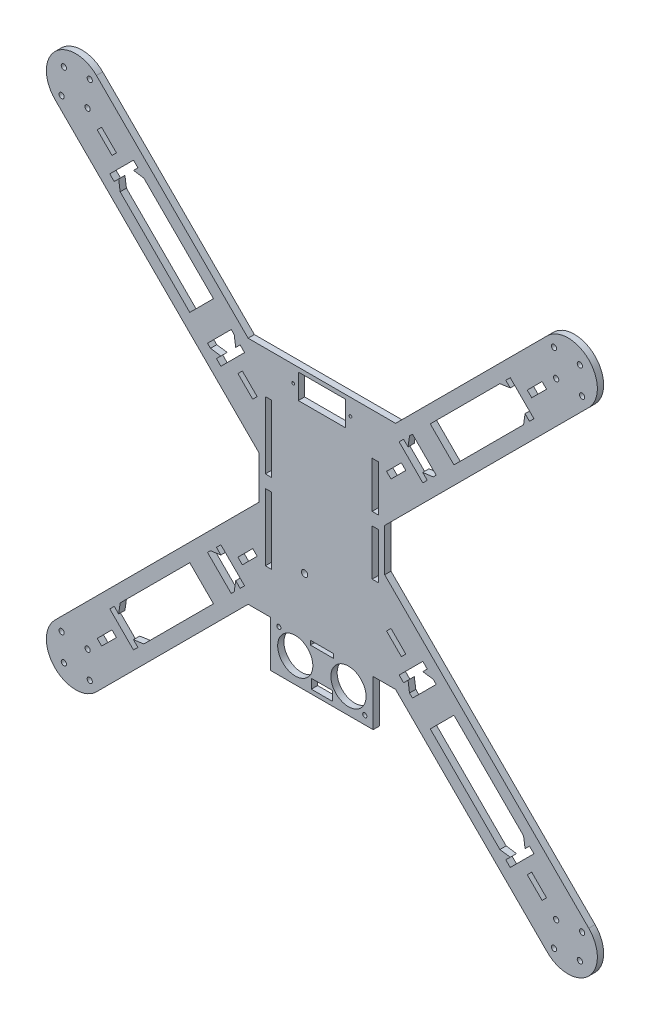
SolidWorks part; units mm, degrees
material "Custom Plastic"
ref_plane "Front Plane" through (0, 0, 0) normal (0, 0, 1) x (1, 0, 0)
ref_plane "Top Plane" through (0, 0, 0) normal (0, 1, 0) x (1, 0, 0)
ref_plane "Right Plane" through (0, 0, 0) normal (1, 0, 0) x (0, 0, -1)
sketch "Sketch1" plane through (0, 0, 0) normal (0, 0, 1) x (1, 0, 0)
  line L0 (117.5, 117.5) -> (-117.5, 117.5) construction
  line L1 (-117.5, 117.5) -> (117.5, -117.5) construction
  line L2 (117.5, -117.5) -> (-117.5, -117.5) construction
  line L3 (-117.5, -117.5) -> (117.5, 117.5) construction
  line L4 (117.5, 117.5) -> (117.5, -117.5) construction
  line L5 (-117.5, 117.5) -> (-117.5, -117.5) construction
  line L6 (0, 117.5) -> (0, -117.5) construction
  line L7 (35.201, 55) -> (-35.201, 55)
  line L8 (-30, 55) -> (30, 55) construction
  line L9 (-35.201, 55) -> (-107.6005, 127.3995)
  line L10 (-127.3995, 107.6005) -> (-30, 10.201)
  line L11 (-117.5, 0) -> (117.5, 0) construction
  line L12 (-30, 10.201) -> (-30, -10.201)
  line L13 (30, 55) -> (30, -55) construction
  line L14 (30, -55) -> (-30, -55) construction
  line L15 (-30, -55) -> (-30, 55) construction
  line L16 (30, 55) -> (-30, -55) construction
  line L17 (-24.5, -55) -> (-24.5, -77)
  line L18 (-127.3995, -107.6005) -> (-30, -10.201)
  line L19 (-24.5, -77) -> (24.5, -77)
  line L20 (-35.201, -55) -> (-107.6005, -127.3995)
  line L21 (35.201, -55) -> (24.5, -55)
  line L22 (35.201, -55) -> (107.6005, -127.3995)
  line L23 (127.3995, -107.6005) -> (30, -10.201)
  line L24 (30, 10.201) -> (30, -10.201)
  line L25 (127.3995, 107.6005) -> (30, 10.201)
  line L26 (35.201, 55) -> (107.6005, 127.3995)
  line L27 (24.5, -55) -> (24.5, -77)
  line L28 (-24.5, -55) -> (-35.201, -55)
  arc A0 (-107.6005, 127.3995) -> (-127.3995, 107.6005) centre (-117.5, 117.5) ccw
  arc A12 (-107.6005, -127.3995) -> (-127.3995, -107.6005) centre (-117.5, -117.5) cw
  arc A16 (107.6005, -127.3995) -> (127.3995, -107.6005) centre (117.5, -117.5) ccw
  arc A24 (107.6005, 127.3995) -> (127.3995, 107.6005) centre (117.5, 117.5) cw
  point P3 (0, 0)
  point P18 (0, 0)
  point P21 (0, -77)
  point P33 (-117.5, 117.5)
  point P34 (-30, 0)
  point P65 (0, -55)
  point P80 (0, 55)
  dimension "D3" = 14
  dimension "D8" = 24.5
  dimension "D7" = 22
  dimension "D1" = 235
  dimension "D2" = 235
  dimension "D4" = 60
  dimension "D5" = 110
  dimension "D6" = 28
extrude "Boss-Extrude1" add sketch "Sketch1" against normal blind 3
sketch "Sketch4" plane through (0, 0, 0) normal (0, 0, 1) x (1, 0, 0)
  line L0 (0, 0) -> (0, 55) construction
  line L1 (35.201, 55) -> (-35.201, 55) construction
  line L2 (0, 0) -> (-30, 0) construction
  line L3 (-30, 10.201) -> (-30, -10.201) construction
  line L4 (-30, 0) -> (-30, 10.201) construction
  line L5 (-30, 10.201) -> (-127.3995, 107.6005) construction
  line L6 (-35.201, 55) -> (-107.6005, 127.3995) construction
  line L7 (-107.6005, 127.3995) -> (-127.3995, 107.6005) construction
  line L8 (-110.7825, 124.2175) -> (-124.2175, 110.7825) construction
  line L9 (-123.1569, 123.1569) -> (-111.8431, 111.8431) construction
  circle A20 centre (-110.7825, 124.2175) radius 1.25
  circle A21 centre (-124.2175, 110.7825) radius 1.25
  circle A22 centre (-123.1569, 123.1569) radius 1.25
  circle A23 centre (-111.8431, 111.8431) radius 1.25
  circle A24 centre (111.8431, 111.8431) radius 1.25
  circle A25 centre (110.7825, 124.2175) radius 1.25
  circle A26 centre (123.1569, 123.1569) radius 1.25
  circle A27 centre (124.2175, 110.7825) radius 1.25
  circle A28 centre (111.8431, -111.8431) radius 1.25
  circle A29 centre (124.2175, -110.7825) radius 1.25
  circle A30 centre (123.1569, -123.1569) radius 1.25
  circle A31 centre (110.7825, -124.2175) radius 1.25
  circle A32 centre (-111.8431, -111.8431) radius 1.25
  circle A33 centre (-110.7825, -124.2175) radius 1.25
  circle A34 centre (-123.1569, -123.1569) radius 1.25
  circle A35 centre (-124.2175, -110.7825) radius 1.25
  point P16 (-117.5, 117.5)
  point P19 (-117.5, 117.5)
  point P26 (-117.5, 117.5)
  point P62 (0, 0)
  dimension "D4" = 2.5
  dimension "D2" = 19
  dimension "D3" = 16
extrude "Cut-Extrude1" cut sketch "Sketch4" against normal blind 3
sketch "Sketch5" plane through (0, 0, 0) normal (0, 0, 1) x (1, 0, 0)
  line L7 (-11.25, 53) -> (-11.25, 41.2)
  line L8 (-11.25, 41.2) -> (11.25, 41.2)
  line L9 (11.25, 41.2) -> (11.25, 53)
  line L10 (11.25, 53) -> (-11.25, 53)
  line L12 (0, 53) -> (0, 41.2) construction
  line L13 (-13.65, 47.1) -> (13.65, 47.1) construction
  line L14 (35.201, 55) -> (-35.201, 55) construction
  circle A2 centre (-13.65, 47.1) radius 0.65
  circle A3 centre (13.65, 47.1) radius 0.65
  point P20 (0, 47.1)
  point P21 (0, 47.1)
  point P26 (0, 55)
  dimension "D8" = 1.3
  dimension "D9" = 1.3
  dimension "D10" = 27.3
  dimension "D11" = 22.5
  dimension "D12" = 11.8
  dimension "D13" = 2
extrude "Cut-Extrude2" cut sketch "Sketch5" against normal blind 3
sketch "Sketch6" plane through (0, 0, 0) normal (0, 0, 1) x (1, 0, 0)
  line L1 (-11.25, 41.2) -> (11.25, 41.2) construction
  circle A0 centre (-8.25, -28.8) radius 1.5
  dimension "D3" = 3
  dimension "D1" = 70
  dimension "D2" = 3
extrude "Cut-Extrude3" cut sketch "Sketch6" against normal blind 3
sketch "Sketch7" plane through (0, 0, 0) normal (0, 0, 1) x (1, 0, 0)
  line L0 (-22.5, -55) -> (-22.5, -75) construction
  line L5 (-22.5, -75) -> (22.5, -75) construction
  line L6 (22.5, -75) -> (22.5, -55) construction
  line L7 (22.5, -55) -> (-22.5, -55) construction
  line L8 (0, -55) -> (0, -75) construction
  line L9 (-12.7, -65) -> (0, -65) construction
  line L10 (-24.5, -77) -> (24.5, -77) construction
  line L11 (-24.5, -55) -> (-24.5, -77) construction
  line L12 (-5.5, -55) -> (-5.5, -57)
  line L13 (-5.5, -57) -> (5.5, -57)
  line L15 (5.5, -55) -> (-5.5, -55)
  line L16 (-5, -75) -> (-5, -70.5)
  line L17 (-5, -70.5) -> (5, -70.5)
  line L21 (5, -75) -> (-5, -75)
  line L22 (5.5, -55) -> (5.5, -57)
  line L23 (5, -75) -> (5, -70.5)
  circle A5 centre (-20.5, -57) radius 1
  circle A6 centre (-12.7, -65) radius 8.4
  circle A7 centre (12.7, -65) radius 8.4
  circle A8 centre (20.5, -73) radius 1
  point P25 (0, -57)
  point P26 (0, -70.5)
  dimension "D3" = 2
  dimension "D6" = 20
  dimension "D13" = 5
  dimension "D5" = 45
  dimension "D1" = 2
  dimension "D4" = 16.8
  dimension "D14" = 2
  dimension "D2" = 2
  dimension "D7" = 2
  dimension "D8" = 2
  dimension "D9" = 12.7
  dimension "D10" = 5.5
  dimension "D11" = 2
  dimension "D12" = 4.5
  dimension "D15" = 2
  dimension "D16" = 2
extrude "Cut-Extrude4" cut sketch "Sketch7" against normal blind 3
sketch "Sketch8" plane through (0, 0, 0) normal (0, 0, 1) x (1, 0, 0)
  line L0 (101.2365, -89.9228) -> (89.9228, -101.2365)
  line L1 (89.9228, -101.2365) -> (87.8015, -99.1152)
  line L2 (36.8898, -48.2035) -> (48.2035, -36.8898)
  line L3 (48.2035, -36.8898) -> (50.3249, -39.0111)
  line L4 (105.4792, -85.6802) -> (85.6802, -105.4792) construction
  line L5 (127.3995, -107.6005) -> (30, -10.201) construction
  line L6 (35.201, -55) -> (107.6005, -127.3995) construction
  line L7 (40.0718, -37.9505) -> (37.9505, -40.0718)
  line L8 (115.8431, -107.8431) -> (111.8431, -111.8431) construction
  line L9 (37.9505, -40.0718) -> (30.8794, -33.0007)
  line L10 (50.3249, 39.0111) -> (48.2035, 36.8898)
  line L11 (30.8794, -33.0007) -> (33.0007, -30.8794)
  line L12 (33.0007, -30.8794) -> (40.0718, -37.9505)
  line L13 (42.5467, -42.5467) -> (39.0111, -39.0111) construction
  line L14 (35.201, -55) -> (107.6005, -127.3995) construction
  line L15 (100.1759, -98.0546) -> (98.0546, -100.1759)
  line L16 (98.0546, -100.1759) -> (105.1256, -107.247)
  line L17 (105.1256, -107.247) -> (107.247, -105.1256)
  line L18 (107.247, -105.1256) -> (100.1759, -98.0546)
  line L19 (99.1152, -99.1152) -> (95.5797, -95.5797) construction
  line L20 (-101.2365, -89.9228) -> (-99.1152, -87.8015)
  line L21 (-100.1759, -98.0546) -> (-107.247, -105.1256)
  line L22 (-107.247, -105.1256) -> (-105.1256, -107.247)
  line L23 (-105.1256, -107.247) -> (-98.0546, -100.1759)
  line L24 (-98.0546, -100.1759) -> (-100.1759, -98.0546)
  line L25 (-89.9228, -101.2365) -> (-101.2365, -89.9228)
  line L26 (-36.8898, -48.2035) -> (-39.0111, -50.3249)
  line L27 (-48.2035, -36.8898) -> (-36.8898, -48.2035)
  line L28 (-37.9505, -40.0718) -> (-40.0718, -37.9505)
  line L29 (-30.8794, -33.0007) -> (-37.9505, -40.0718)
  line L30 (-40.0718, -37.9505) -> (-33.0007, -30.8794)
  line L31 (-33.0007, -30.8794) -> (-30.8794, -33.0007)
  line L32 (-89.9228, 101.2365) -> (-87.8015, 99.1152)
  line L33 (-98.0546, 100.1759) -> (-105.1256, 107.247)
  line L34 (-105.1256, 107.247) -> (-107.247, 105.1256)
  line L35 (-107.247, 105.1256) -> (-100.1759, 98.0546)
  line L36 (-100.1759, 98.0546) -> (-98.0546, 100.1759)
  line L37 (-101.2365, 89.9228) -> (-89.9228, 101.2365)
  line L38 (-48.2035, 36.8898) -> (-50.3249, 39.0111)
  line L39 (-36.8898, 48.2035) -> (-48.2035, 36.8898)
  line L40 (-40.0718, 37.9505) -> (-37.9505, 40.0718)
  line L41 (-33.0007, 30.8794) -> (-40.0718, 37.9505)
  line L42 (-37.9505, 40.0718) -> (-30.8794, 33.0007)
  line L43 (-30.8794, 33.0007) -> (-33.0007, 30.8794)
  line L44 (101.2365, 89.9228) -> (99.1152, 87.8015)
  line L45 (100.1759, 98.0546) -> (107.247, 105.1256)
  line L46 (107.247, 105.1256) -> (105.1256, 107.247)
  line L47 (105.1256, 107.247) -> (98.0546, 100.1759)
  line L48 (98.0546, 100.1759) -> (100.1759, 98.0546)
  line L49 (89.9228, 101.2365) -> (101.2365, 89.9228)
  line L50 (36.8898, 48.2035) -> (39.0111, 50.3249)
  line L51 (48.2035, 36.8898) -> (36.8898, 48.2035)
  line L52 (37.9505, 40.0718) -> (40.0718, 37.9505)
  line L53 (30.8794, 33.0007) -> (37.9505, 40.0718)
  line L54 (40.0718, 37.9505) -> (33.0007, 30.8794)
  line L55 (33.0007, 30.8794) -> (30.8794, 33.0007)
  line L56 (30, 10.201) -> (127.3995, 107.6005) construction
  line L57 (41.8396, 53.1533) -> (84.9731, 96.2868)
  line L58 (96.2868, 84.9731) -> (53.1533, 41.8396)
  line L59 (87.8015, 99.1152) -> (89.9228, 101.2365)
  line L60 (99.1152, -87.8015) -> (96.9939, -89.9228)
  line L61 (-96.2868, -84.9731) -> (-53.1533, -41.8396)
  line L62 (96.9939, -89.9228) -> (96.2868, -84.9731)
  line L63 (99.1152, -87.8015) -> (101.2365, -89.9228)
  line L64 (87.8015, -99.1152) -> (89.9228, -96.9939)
  line L65 (-87.8015, -99.1152) -> (-89.9228, -101.2365)
  line L66 (89.9228, -96.9939) -> (84.9731, -96.2868)
  line L67 (84.9731, -96.2868) -> (41.8396, -53.1533)
  line L68 (50.3249, -39.0111) -> (48.2035, -41.1325)
  line L69 (48.2035, -41.1325) -> (53.1533, -41.8396)
  line L70 (53.1533, -41.8396) -> (96.2868, -84.9731)
  line L71 (39.0111, -50.3249) -> (41.1325, -48.2035)
  line L72 (41.1325, -48.2035) -> (41.8396, -53.1533)
  line L73 (39.0111, -50.3249) -> (36.8898, -48.2035)
  line L74 (-89.9228, -96.9939) -> (-84.9731, -96.2868)
  line L75 (-87.8015, -99.1152) -> (-89.9228, -96.9939)
  line L76 (-96.9939, -89.9228) -> (-96.2868, -84.9731)
  line L77 (-99.1152, -87.8015) -> (-96.9939, -89.9228)
  line L78 (-41.1325, -48.2035) -> (-41.8396, -53.1533)
  line L79 (-39.0111, -50.3249) -> (-41.1325, -48.2035)
  line L80 (-48.2035, -41.1325) -> (-53.1533, -41.8396)
  line L81 (-50.3249, -39.0111) -> (-48.2035, -41.1325)
  line L82 (-96.9939, 89.9228) -> (-96.2868, 84.9731)
  line L83 (-99.1152, 87.8015) -> (-96.9939, 89.9228)
  line L84 (-89.9228, 96.9939) -> (-84.9731, 96.2868)
  line L85 (-87.8015, 99.1152) -> (-89.9228, 96.9939)
  line L86 (-48.2035, 41.1325) -> (-53.1533, 41.8396)
  line L87 (-50.3249, 39.0111) -> (-48.2035, 41.1325)
  line L88 (-41.1325, 48.2035) -> (-41.8396, 53.1533)
  line L89 (-39.0111, 50.3249) -> (-41.1325, 48.2035)
  line L90 (89.9228, 96.9939) -> (84.9731, 96.2868)
  line L91 (87.8015, 99.1152) -> (89.9228, 96.9939)
  line L92 (96.9939, 89.9228) -> (96.2868, 84.9731)
  line L93 (99.1152, 87.8015) -> (96.9939, 89.9228)
  line L94 (41.1325, 48.2035) -> (41.8396, 53.1533)
  line L95 (39.0111, 50.3249) -> (41.1325, 48.2035)
  line L96 (48.1429, 41.1931) -> (53.1533, 41.8396)
  line L97 (50.3249, 39.0111) -> (48.1429, 41.1931)
  line L98 (-39.0111, 50.3249) -> (-36.8898, 48.2035)
  line L99 (-53.1533, 41.8396) -> (-96.2868, 84.9731)
  line L100 (-99.1152, 87.8015) -> (-101.2365, 89.9228)
  line L101 (-84.9731, 96.2868) -> (-41.8396, 53.1533)
  line L102 (-41.8396, -53.1533) -> (-84.9731, -96.2868)
  line L103 (-50.3249, -39.0111) -> (-48.2035, -36.8898)
  line L104 (96.2868, 84.9731) -> (84.9731, 96.2868) construction
  line L105 (53.1533, 41.8396) -> (41.8396, 53.1533) construction
  point P10 (95.5797, -95.5797)
  point P11 (95.5797, -95.5797)
  point P18 (-49.2642, 40.0718)
  point P19 (-49.2642, -40.0718)
  point P68 (0, 0)
  point P122 (0, 0)
  dimension "D1" = 23
  dimension "D2" = 75
  dimension "D3" = 3
  dimension "D4" = 10
  dimension "D5" = 5
  dimension "D6" = 6
  dimension "D7" = 3
  dimension "D8" = 10
  dimension "D9" = 5
  dimension "D11" = 6
  dimension "D12" = 3
  dimension "D13" = 4
  dimension "D14" = 3
  dimension "D15" = 3
  dimension "D16" = 4
  dimension "D17" = 3
  dimension "D18" = 3
  dimension "D19" = 4
  dimension "D20" = 3
  dimension "D21" = 3
  dimension "D22" = 4
  dimension "D23" = 3
  dimension "D24" = 3
  dimension "D25" = 4
  dimension "D26" = 3
  dimension "D27" = 4
  dimension "D28" = 3
  dimension "D29" = 3
  dimension "D30" = 4
  dimension "D31" = 4
  dimension "D32" = 3
  dimension "D33" = 3
  dimension "D34" = 4
  dimension "D35" = 4
  dimension "D36" = 3
  dimension "D37" = 3
  dimension "D38" = 4
  dimension "D39" = 4
  dimension "D40" = 3
  dimension "D41" = 3
  dimension "D42" = 4
  dimension "D43" = 4
  dimension "D10" = 4
extrude "Cut-Extrude5" cut sketch "Sketch8" against normal through all
sketch "Sketch9" plane through (-5.6569, 5.6569, 0) normal (0.7071, -0.7071, 0) x (0, 0, -1)
  line L0 (3, 128.1701) -> (3, 67.1701) construction
  line L1 (3, 81.1701) -> (0, 81.1701)
  line L2 (3, 81.1701) -> (3, 69.1701)
  line L3 (3, 69.1701) -> (0, 69.1701)
  line L4 (0, 81.1701) -> (0, 69.1701)
  line L5 (0, 128.1701) -> (0, 67.1701) construction
  line L6 (0, 0) -> (28.0274, 0) construction
  line L7 (3, 63.1701) -> (0, 63.1701) construction
  dimension "D1" = 6
  dimension "D2" = 12
extrude "Boss-Extrude2" add sketch "Sketch9" along normal up to next
sketch "Sketch11" plane through (5.6569, 5.6569, 0) normal (-0.7071, -0.7071, 0) x (0, 0, 1)
  line L0 (-3, -128.1701) -> (-3, -67.1701) construction
  line L1 (-3, -69.1701) -> (0, -69.1701)
  line L2 (-3, -69.1701) -> (-3, -81.1701)
  line L3 (-3, -81.1701) -> (0, -81.1701)
  line L4 (0, -69.1701) -> (0, -81.1701)
  line L5 (0, -128.1701) -> (0, -67.1701) construction
  line L6 (-3, -63.1701) -> (0, -63.1701) construction
  dimension "D1" = 6
  dimension "D2" = 12
extrude "Boss-Extrude3" add sketch "Sketch11" along normal up to next
sketch "Sketch12" plane through (5.6569, -5.6569, 0) normal (-0.7071, 0.7071, 0) x (0, 0, 1)
  line L0 (-3, -128.1701) -> (-3, -67.1701) construction
  line L1 (-3, -69.1701) -> (0, -69.1701)
  line L2 (-3, -69.1701) -> (-3, -81.1701)
  line L3 (-3, -81.1701) -> (0, -81.1701)
  line L4 (0, -69.1701) -> (0, -81.1701)
  line L5 (0, -128.1701) -> (0, -67.1701) construction
  dimension "D1" = 6
  dimension "D2" = 12
extrude "Boss-Extrude4" add sketch "Sketch12" along normal up to next
sketch "Sketch13" plane through (5.6569, 5.6569, 0) normal (-0.7071, -0.7071, 0) x (0, 0, 1)
  line L0 (-3, 67.1701) -> (-3, 128.1701) construction
  line L1 (-3, 69.1701) -> (0, 69.1701)
  line L2 (-3, 69.1701) -> (-3, 81.1701)
  line L3 (-3, 81.1701) -> (0, 81.1701)
  line L4 (0, 69.1701) -> (0, 81.1701)
  line L5 (0, 67.1701) -> (0, 128.1701) construction
  dimension "D1" = 6
  dimension "D2" = 12
extrude "Boss-Extrude5" add sketch "Sketch13" along normal up to next
sketch "Sketch14" plane through (0, 0, -3) normal (0, 0, -1) x (-1, 0, 0)
  line L0 (30, 0) -> (-30, 0) construction
  line L1 (30, 10.201) -> (30, -10.201) construction
  line L2 (-30, -10.201) -> (-30, 10.201) construction
  line L3 (25.5, -3) -> (25.5, 3) construction
  line L4 (27, -3) -> (24, -3)
  line L5 (27, -3) -> (27, -35)
  line L6 (27, -35) -> (24, -35)
  line L7 (24, -3) -> (24, -35)
  line L8 (27, 3) -> (24, 3)
  line L9 (27, 3) -> (27, 35)
  line L10 (27, 35) -> (24, 35)
  line L11 (24, 3) -> (24, 35)
  line L12 (24, -35) -> (-25.5, -35) construction
  line L13 (-25.5, -35) -> (-25.5, -15) construction
  line L15 (-24, -15) -> (-27, -15)
  line L16 (-24, -15) -> (-24, 7)
  line L17 (-24, 7) -> (-27, 7)
  line L18 (-27, -15) -> (-27, 7)
  line L19 (-24, 13) -> (-27, 13)
  line L20 (-24, 13) -> (-24, 35)
  line L21 (-24, 35) -> (-27, 35)
  line L22 (-27, 13) -> (-27, 35)
  point P16 (25.5, 0)
  point P23 (-25.5, -15)
  point P28 (-25.5, 13)
  dimension "D1" = 6
  dimension "D2" = 32
  dimension "D3" = 3
  dimension "D4" = 3
  dimension "D5" = 20
  dimension "D6" = 4.5
  dimension "D7" = 6
  dimension "D8" = 22
  dimension "D9" = 3
extrude "Cut-Extrude6" cut sketch "Sketch14" against normal through all
